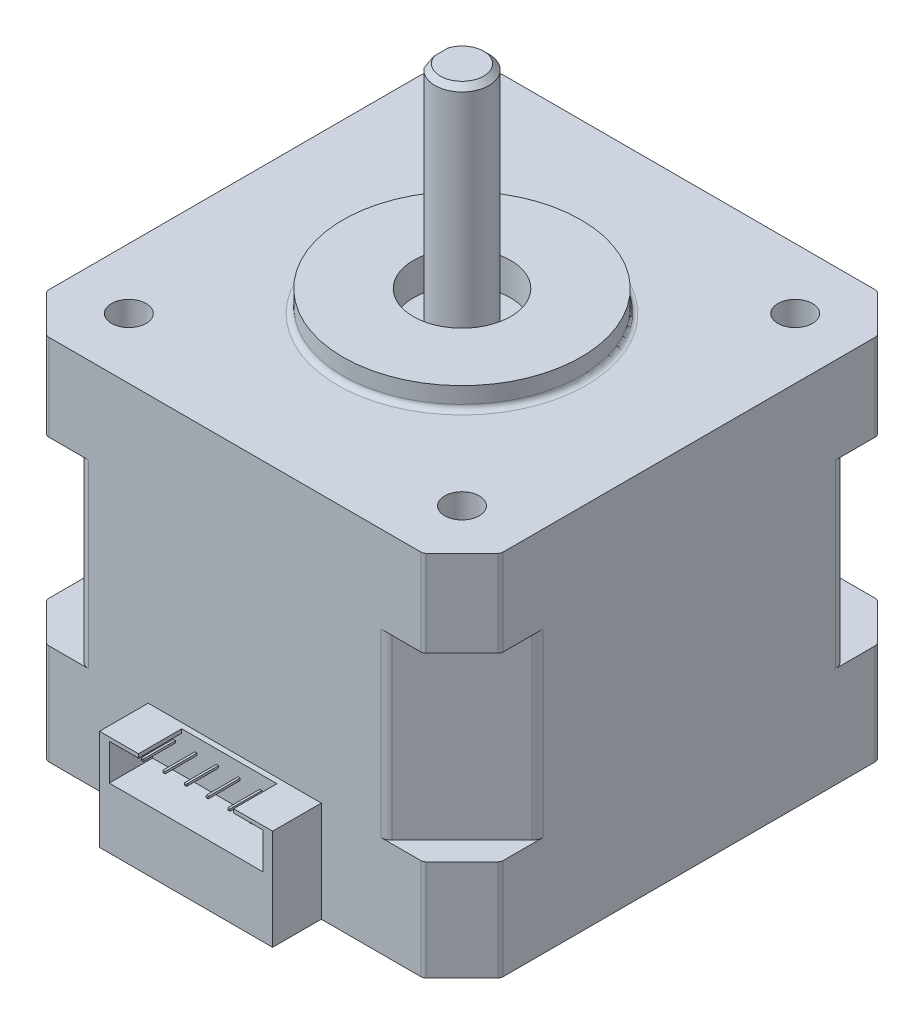
SolidWorks part; units mm, degrees
ref_plane "Płaszczyzna przednia" through (0, 0, 0) normal (0, 0, 1) x (1, 0, 0)
ref_plane "Płaszczyzna górna" through (0, 0, 0) normal (0, 1, 0) x (1, 0, 0)
ref_plane "Płaszczyzna prawa" through (0, 0, 0) normal (1, 0, 0) x (0, 0, -1)
sketch "Szkic1" plane through (0, 0, 0) normal (0, 1, 0) x (1, 0, 0)
  line L1 (0, 0) -> (42, 0)
  line L2 (0, 0) -> (0, 42)
  line L3 (0, 42) -> (42, 42)
  line L4 (42, 0) -> (42, 42)
  dimension "D1" = 42
  dimension "D2" = 42
extrude "Dodanie-wyciągnięcie1" add sketch "Szkic1" along normal blind 9.3
chamfer "Sfazowanie1" distance 3.6 angle 45 4 edges at (0, 4.65, -42) (0, 4.65, 0) (42, 4.65, -42) (42, 4.65, 0)
fillet "Zaokrąglenie1" radius 0.5 8 edges at (42, 4.65, -3.6) (38.4, 4.65, 0) (38.4, 4.65, -42) (42, 4.65, -38.4) (3.6, 4.65, -42) (0, 4.65, -38.4) (3.6, 4.65, 0) (0, 4.65, -3.6)
sketch "Szkic2" plane through (0, 9.3, 0) normal (0, 1, 0) x (1, 0, 0)
  line L0 (42, 3.8071) -> (42, 38.1929) construction
  line L1 (0, 0) -> (42, 0)
  line L2 (0, 0) -> (0, 42)
  line L3 (0, 42) -> (42, 42)
  line L4 (42, 0) -> (42, 42)
  line L5 (38.1929, 42) -> (3.8071, 42) construction
extrude "Dodanie-wyciągnięcie2" add sketch "Szkic2" along normal blind 16.7
sketch "Szkic4" plane through (0, 26, 0) normal (0, 1, 0) x (1, 0, 0)
  line L0 (34.9289, 0) -> (42, 7.0711)
  line L1 (0, 0) -> (42, 0) construction
  line L2 (42, 0) -> (42, 42) construction
  line L3 (42, 7.0711) -> (42, 0)
  line L4 (42, 0) -> (34.9289, 0)
  line L5 (0, 21) -> (42, 21) construction
  line L6 (0, 42) -> (0, 0) construction
  line L7 (21, 0) -> (21, 42) construction
  line L8 (42, 42) -> (0, 42) construction
  line L9 (42, 34.9289) -> (42, 42)
  line L10 (34.9289, 42) -> (42, 34.9289)
  line L11 (42, 42) -> (34.9289, 42)
  line L12 (7.0711, 42) -> (0, 34.9289)
  line L13 (0, 42) -> (7.0711, 42)
  line L14 (0, 34.9289) -> (0, 42)
  line L15 (0, 7.0711) -> (0, 0)
  line L16 (7.0711, 0) -> (0, 7.0711)
  line L17 (0, 0) -> (7.0711, 0)
  dimension "D1" = 45
  dimension "D2" = 10
extrude "Wytnij-wyciągnięcie1" cut sketch "Szkic4" against normal up to vertex (16.7 mm away) up to point (38.5464, 9.3, -0.1464)
fillet "Zaokrąglenie2" radius 1 8 edges at (0, 17.65, -7.0711) (7.0711, 17.65, 0) (0, 17.65, -34.9289) (7.0711, 17.65, -42) (34.9289, 17.65, -42) (42, 17.65, -34.9289) (34.9289, 17.65, 0) (42, 17.65, -7.0711)
sketch "Szkic3" plane through (0, 26, 0) normal (0, 1, 0) x (1, 0, 0)
  line L1 (0, 0) -> (42, 0)
  line L2 (0, 0) -> (0, 42)
  line L3 (0, 42) -> (42, 42)
  line L4 (42, 0) -> (42, 42)
extrude "Dodanie-wyciągnięcie3" add sketch "Szkic3" along normal blind 8
chamfer "Sfazowanie3" distance 3.6 angle 45 4 edges at (0, 30, 0) (0, 30, -42) (42, 30, 0) (42, 30, -42)
fillet "Zaokrąglenie3" radius 0.5 8 edges at (42, 30, -3.6) (38.4, 30, 0) (3.6, 30, 0) (0, 30, -3.6) (0, 30, -38.4) (3.6, 30, -42) (38.4, 30, -42) (42, 30, -38.4)
sketch "Szkic5" plane through (0, 0, 0) normal (0, -1, 0) x (1, 0, 0)
  line L0 (0, -21) -> (42, -21) construction
  line L1 (0, -38.1929) -> (0, -3.8071) construction
  line L2 (42, -3.8071) -> (42, -38.1929) construction
  line L3 (21, 0) -> (21, -42) construction
  line L4 (3.8071, 0) -> (38.1929, 0) construction
  line L5 (38.1929, -42) -> (3.8071, -42) construction
  circle A0 centre (21, -21) radius 4.5
  point P12 (21, -21)
  dimension "D1" = 9
extrude "Wytnij-wyciągnięcie2" cut sketch "Szkic5" against normal blind 4
sketch "Szkic6" plane through (0, 0, 0) normal (0, -1, 0) x (1, 0, 0)
  line L0 (0, -38.1929) -> (0, -3.8071) construction
  line L1 (3.8071, 0) -> (38.1929, 0) construction
  line L2 (21, 0) -> (21, -42) construction
  line L3 (38.1929, -42) -> (3.8071, -42) construction
  line L4 (0, -21) -> (42, -21) construction
  circle A0 centre (5.6, -5.6) radius 3
  circle A1 centre (36.4, -5.6) radius 3
  circle A2 centre (36.4, -36.4) radius 3
  circle A3 centre (5.6, -36.4) radius 3
  dimension "D1" = 6
  dimension "D2" = 5.6
  dimension "D3" = 5.6
extrude "Wytnij-wyciągnięcie3" cut sketch "Szkic6" against normal blind 8
sketch "Szkic7" plane through (0, 34, 0) normal (0, 1, 0) x (1, 0, 0)
  line L0 (42, 3.8071) -> (42, 38.1929) construction
  line L1 (3.8071, 0) -> (38.1929, 0) construction
  line L2 (21, 0) -> (21, 42) construction
  line L3 (38.1929, 42) -> (3.8071, 42) construction
  line L4 (42, 21) -> (0, 21) construction
  line L5 (0, 38.1929) -> (0, 3.8071) construction
  circle A0 centre (36.4, 5.6) radius 1.6
  circle A1 centre (5.6, 5.6) radius 1.6
  circle A2 centre (5.6, 36.4) radius 1.6
  circle A3 centre (36.4, 36.4) radius 1.6
  point P14 (21, 21)
  dimension "D1" = 3.2
  dimension "D2" = 5.6
  dimension "D3" = 5.6
extrude "Wytnij-wyciągnięcie4" cut sketch "Szkic7" against normal through all
sketch "Szkic20" plane through (0, 34, 0) normal (0, 1, 0) x (1, 0, 0)
  circle A0 centre (21, 21) radius 11
  dimension "D1" = 22
extrude "Dodanie-wyciągnięcie4" add sketch "Szkic20" along normal blind 2
fillet "Zaokrąglenie4" radius 0.5 1 edges at (21, 34, -32)
sketch "Szkic21" plane through (0, 36, 0) normal (0, 1, 0) x (1, 0, 0)
  circle A0 centre (21, 21) radius 4.5
  dimension "D1" = 9
extrude "Wytnij-wyciągnięcie6" cut sketch "Szkic21" against normal blind 3
sketch "Szkic22" plane through (0, 33, 0) normal (0, 1, 0) x (1, 0, 0)
  line L0 (19.1, 19.3752) -> (19.1, 22.6248)
  arc A0 (19.1, 19.3752) -> (19.1, 22.6248) centre (21, 21) ccw
  dimension "D1" = 5
  dimension "D2" = 1.9
extrude "Dodanie-wyciągnięcie5" add sketch "Szkic22" along normal blind 21
chamfer "Sfazowanie4" distance 0.5 angle 45 1 edges at (23.5, 54, -21)
sketch "Szkic23" plane through (0, 0, 0) normal (0, 0, 1) x (1, 0, 0)
  line L0 (3.8071, 0) -> (38.1929, 0) construction
  line L1 (28.9929, 0) -> (12.9929, 0)
  line L2 (28.9929, 0) -> (28.9929, 9.3)
  line L3 (28.9929, 9.3) -> (12.9929, 9.3)
  line L4 (12.9929, 0) -> (12.9929, 9.3)
  line L5 (38.1929, 0) -> (38.1929, 9.3) construction
  line L6 (3.8071, 9.3) -> (3.8071, 0) construction
  line L7 (3.8071, 9.3) -> (7.4853, 9.3) construction
  dimension "D1" = 16
  dimension "D2" = 9.2
  dimension "D3" = 9.1858
extrude "Dodanie-wyciągnięcie6" add sketch "Szkic23" along normal blind 4.5
sketch "Szkic24" plane through (0, 0, 4.5) normal (0, 0, 1) x (1, 0, 0)
  line L0 (16.5929, 9.3) -> (16.5929, 8.95)
  line L1 (28.9929, 9.3) -> (12.9929, 9.3) construction
  line L2 (16.5929, 8.95) -> (13.8929, 8.95)
  line L3 (13.8929, 8.95) -> (13.8929, 5.6)
  line L4 (13.8929, 5.6) -> (28.0929, 5.6)
  line L5 (28.0929, 5.6) -> (28.0929, 8.95)
  line L6 (28.0929, 8.95) -> (25.3929, 8.95)
  line L7 (25.3929, 8.95) -> (25.3929, 9.3)
  line L8 (25.3929, 9.3) -> (16.5929, 9.3)
  line L9 (12.9929, 9.3) -> (12.9929, 0) construction
  line L10 (28.9929, 0) -> (28.9929, 9.3) construction
  line L11 (12.9929, 0) -> (28.9929, 0) construction
  dimension "D1" = 0.35
  dimension "D2" = 0.9
  dimension "D3" = 0.35
  dimension "D4" = 0.9
  dimension "D5" = 5.6
  dimension "D6" = 3.6
  dimension "D7" = 3.6
extrude "Wytnij-wyciągnięcie7" cut sketch "Szkic24" against normal blind 4
sketch "Szkic25" plane through (0, 0, 0.5) normal (0, 0, 1) x (1, 0, 0)
  line L0 (16.5929, 8.95) -> (13.8929, 8.95) construction
  line L1 (13.8929, 8.95) -> (13.8929, 5.6) construction
  line L4 (15.9929, 8.0528) -> (15.9929, 7.8528)
  line L5 (17.9929, 8.0528) -> (17.9929, 7.8528)
  line L6 (19.9929, 8.0528) -> (19.9929, 7.8528)
  line L7 (21.9929, 8.0528) -> (21.9929, 7.8528)
  line L8 (23.9929, 8.0528) -> (23.9929, 7.8528)
  line L9 (25.9929, 8.0528) -> (25.9929, 7.8528)
  point P0 (15.9929, 7.9528)
  point P7 (17.9929, 7.9528)
  point P8 (19.9929, 7.9528)
  point P9 (21.9929, 7.9528)
  point P10 (23.9929, 7.9528)
  point P11 (25.9929, 7.9528)
  point P14 (17.9929, 7.9528)
  point P18 (15.9929, 7.9528)
  dimension "D1" = 0.9972
  dimension "D2" = 2.1
  dimension "D4" = 0.2
  dimension "D3" = 6
  dimension "D5" = 5
extrude "Wyciągnięcie-cienka ścianka2" add sketch "Szkic25" along normal blind 3 thin thin type one direction wall 0.2
fillet "Zaokrąglenie6" radius 0.1 24 edges at (25.8929, 8.0528, 3.5) (25.9929, 7.9528, 3.5) (25.8929, 7.8528, 3.5) (25.7929, 7.9528, 3.5) (23.8929, 8.0528, 3.5) (23.9929, 7.9528, 3.5) (23.8929, 7.8528, 3.5) (23.7929, 7.9528, 3.5) (21.8929, 8.0528, 3.5) (21.9929, 7.9528, 3.5) (21.8929, 7.8528, 3.5) (21.7929, 7.9528, 3.5) (19.8929, 8.0528, 3.5) (19.9929, 7.9528, 3.5) (19.8929, 7.8528, 3.5) (19.7929, 7.9528, 3.5) (17.8929, 8.0528, 3.5) (17.9929, 7.9528, 3.5) (17.8929, 7.8528, 3.5) (17.7929, 7.9528, 3.5) (15.8929, 8.0528, 3.5) (15.9929, 7.9528, 3.5) (15.8929, 7.8528, 3.5) (15.7929, 7.9528, 3.5)
